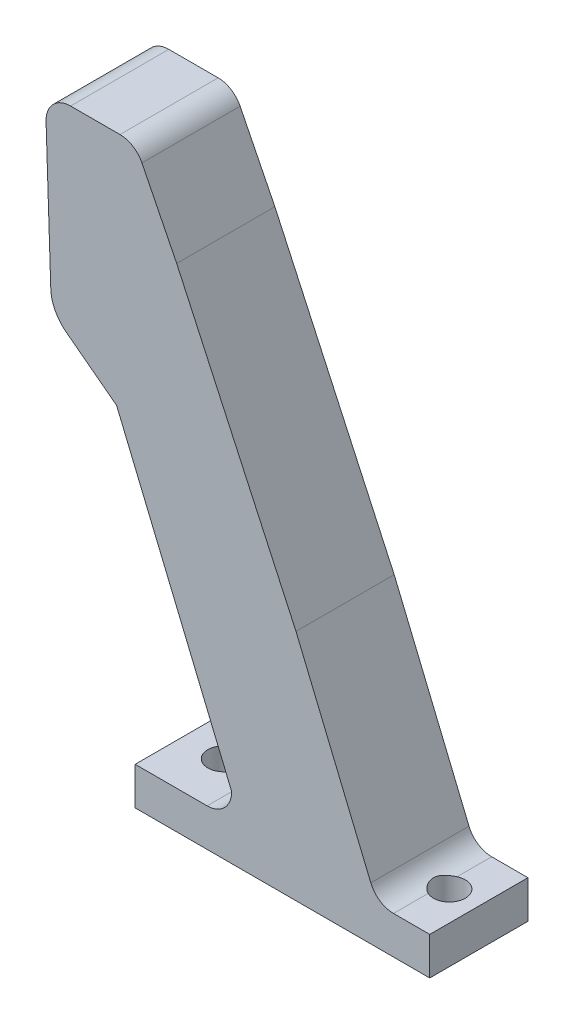
SolidWorks part; units mm, degrees
ref_plane "Front Plane" through (0, 0, 0) normal (0, 0, 1) x (1, 0, 0)
ref_plane "Top Plane" through (0, 0, 0) normal (0, 1, 0) x (1, 0, 0)
ref_plane "Right Plane" through (0, 0, 0) normal (1, 0, 0) x (0, 0, -1)
sketch "Sketch1" plane through (0, 0, 0) normal (0, 0, 1) x (1, 0, 0)
  line L2 (-44.0978, -29.1565) -> (-44.0978, -36.8501)
  line L3 (-44.0978, -36.8501) -> (15.9022, -36.8501)
  line L7 (-35.9155, -29.1565) -> (-44.0978, -29.1565)
  line L10 (-58.1484, 40.0615) -> (-47.8781, 32.2588)
  line L14 (-29.4383, -29.1565) -> (-35.9155, -29.1565)
  line L15 (15.9022, -36.8501) -> (15.9022, -29.1565)
  line L16 (15.9022, -29.1565) -> (8.5166, -29.1565)
  line L18 (-47.8781, 32.2588) -> (-24.4383, -24.1565)
  line L19 (15.8445, -36.8501) -> (15.9599, -36.8501) construction
  line L20 (3.898, -26.0718) -> (-11.3405, 10.674)
  line L21 (-11.3405, 10.674) -> (-35.6415, 63.4231)
  line L26 (-61.2932, 46.4002) -> (-62.2447, 75.2171)
  line L27 (-57.2475, 80.3821) -> (-47.1917, 80.3821)
  line L28 (-42.7172, 77.6133) -> (-35.6415, 63.4231)
  arc A7 (-61.2932, 46.4002) -> (-58.1484, 40.0615) centre (-53.3327, 46.4002) ccw
  arc A13 (8.5166, -29.1565) -> (3.898, -26.0718) centre (8.5166, -24.1565) cw
  arc A14 (-24.4383, -24.1565) -> (-29.4383, -29.1565) centre (-29.4383, -24.1565) cw
  arc A17 (-62.2447, 75.2171) -> (-57.2475, 80.3821) centre (-57.2475, 75.3821) cw
  arc A18 (-47.1917, 80.3821) -> (-42.7172, 77.6133) centre (-47.1917, 75.3821) cw
  point P0 (-24.4383, -23.2783)
  dimension "D1" = 5
  dimension "D2" = 5
extrude "Boss-Extrude1" add sketch "Sketch1" along normal blind 20
sketch "Sketch3" plane through (0, -29.1565, 0) normal (0, 1, 0) x (1, 0, 0)
  line L0 (15.9022, -20) -> (15.9022, 0) construction
  circle A0 centre (9.9022, -10) radius 3.25
  circle A1 centre (-36.0384, -10) radius 3.25
  dimension "D2" = 6.5
  dimension "D3" = 6.5
  dimension "D1" = 6
extrude "Cut-Extrude1" cut sketch "Sketch3" against normal blind 20 and the other way blind 20
